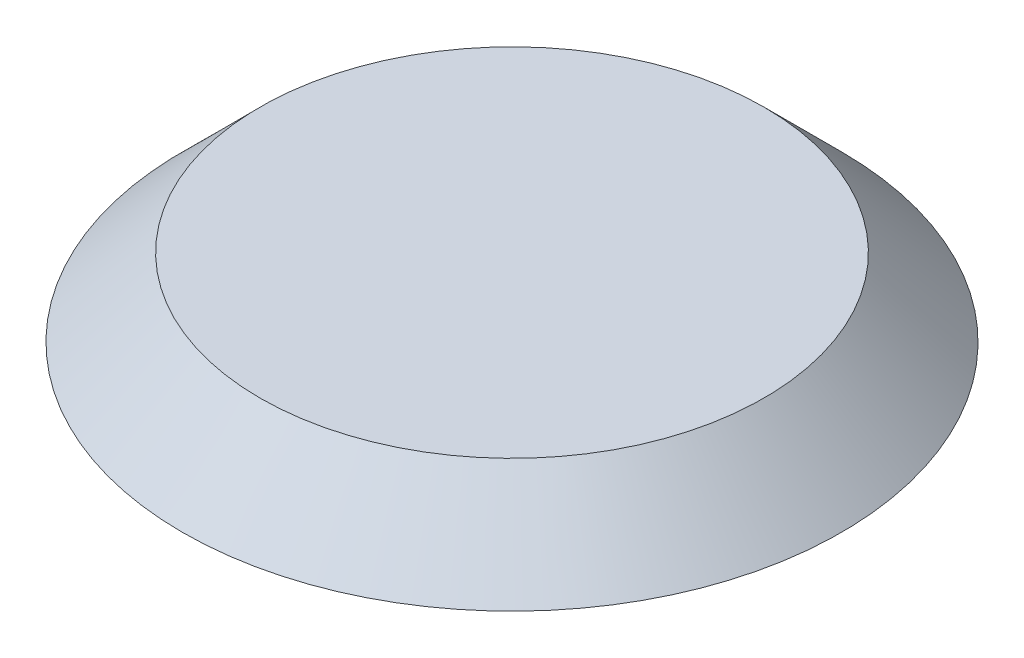
SolidWorks part; units mm, degrees
ref_plane "Front Plane" through (0, 0, 0) normal (0, 0, 1) x (1, 0, 0)
ref_plane "Top Plane" through (0, 0, 0) normal (0, 1, 0) x (1, 0, 0)
ref_plane "Right Plane" through (0, 0, 0) normal (1, 0, 0) x (0, 0, -1)
sketch "Sketch1" plane through (0, 0, 0) normal (0, 1, 0) x (1, 0, 0)
  circle A0 centre (0, 0) radius 8.5
  dimension "D1" = 17
extrude "Boss-Extrude1" add sketch "Sketch1" along normal blind 2
chamfer "Chamfer1" distance 2 angle 45 1 edges at (0, 2, 8.5)
sketch "Sketch2" plane through (0, 0, 0) normal (0, -1, 0) x (-1, 0, 0)
  circle A0 centre (0, 0) radius 0.8
  dimension "D1" = 1.6
extrude "Boss-Extrude2" add sketch "Sketch2" along normal blind 0.4 contours A0
